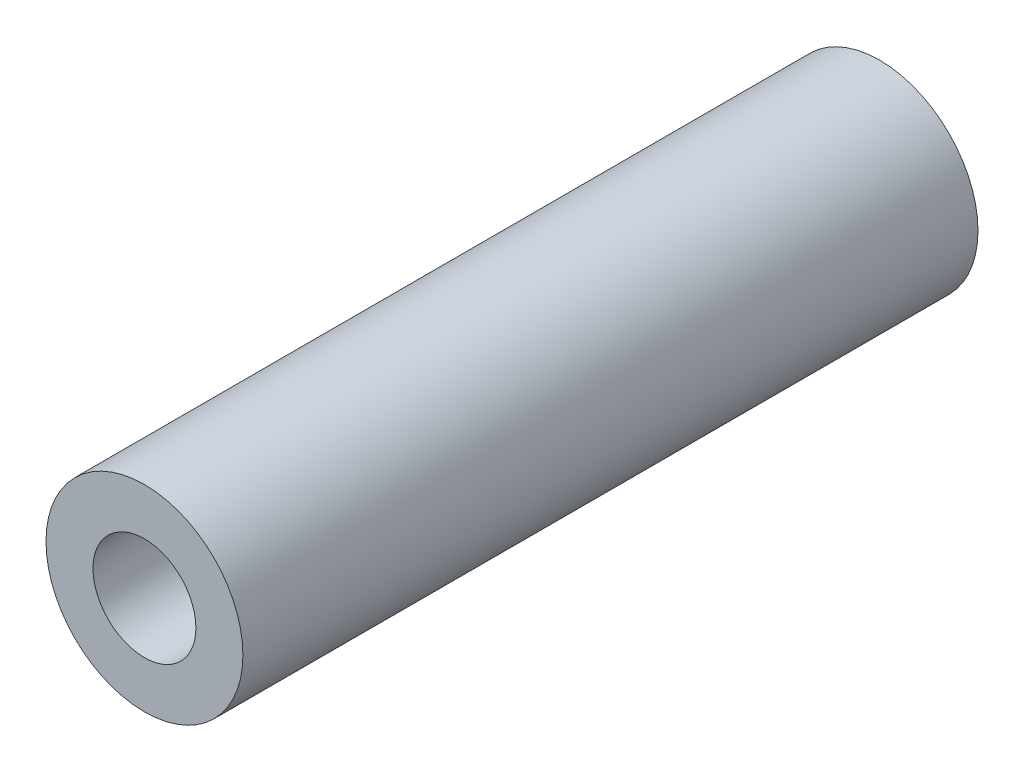
SolidWorks part; units mm, degrees
material "6061-T6 (SS)"
ref_plane "Front Plane" through (0, 0, 0) normal (0, 0, 1) x (1, 0, 0)
ref_plane "Top Plane" through (0, 0, 0) normal (0, 1, 0) x (1, 0, 0)
ref_plane "Right Plane" through (0, 0, 0) normal (1, 0, 0) x (0, 0, -1)
sketch "Sketch1" plane through (0, 0, 0) normal (0, 0, 1) x (1, 0, 0)
  circle A0 centre (0, 0) radius 2.4892
  circle A1 centre (0, 0) radius 4.7625
  dimension "D1" = 4.9784
  dimension "D2" = 9.525
extrude "Boss-Extrude1" add sketch "Sketch1" along normal mid plane 35.56
